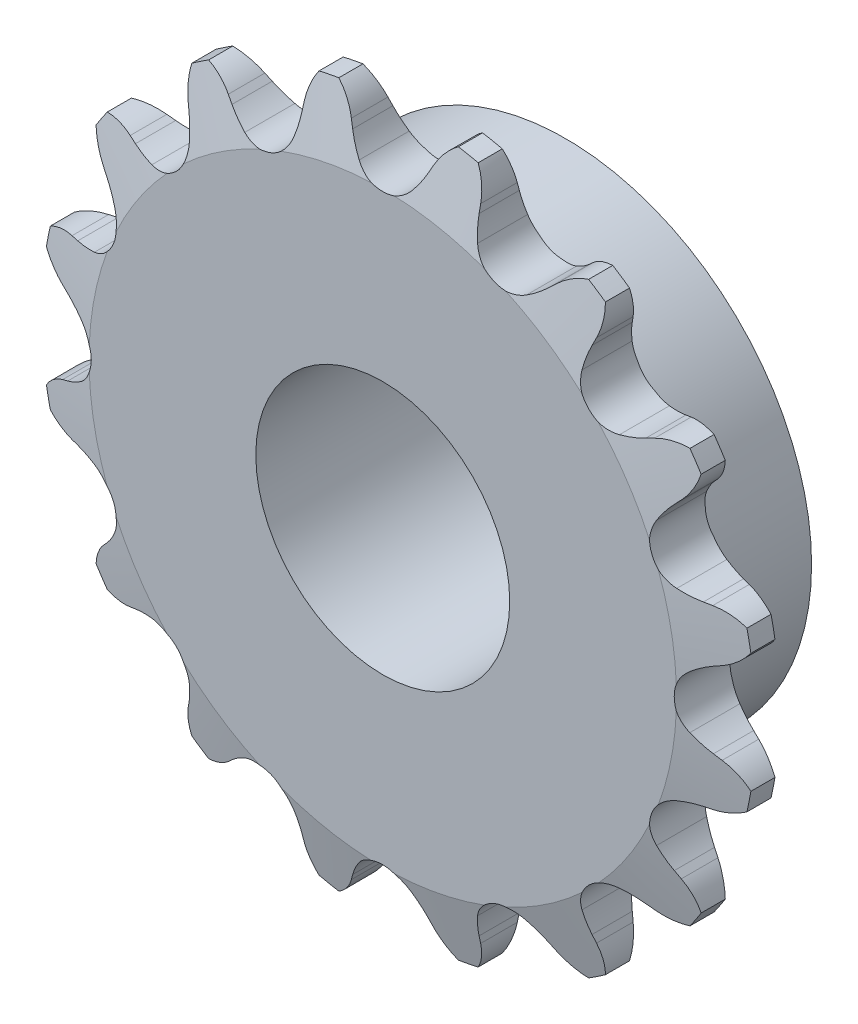
SolidWorks part; units mm, degrees
ref_plane "Front Plane" through (0, 0, 0) normal (0, 0, 1) x (1, 0, 0)
ref_plane "Top Plane" through (0, 0, 0) normal (0, 1, 0) x (1, 0, 0)
ref_plane "Right Plane" through (0, 0, 0) normal (1, 0, 0) x (0, 0, -1)
ref_axis "Axis1" through (0, 0, -88.99) along (0, 0, 1)
sketch "Sprocket-BaseSketch" plane through (0, 0, 0) normal (1, 0, 0) x (0, 0, -1)
  line L0 (1.397, 0) -> (1.397, 14.6918)
  line L1 (1.397, 14.6918) -> (0.6032, 17.8668)
  line L2 (0.6032, 17.8668) -> (-0.6032, 17.8668)
  line L3 (-0.6032, 17.8668) -> (-1.397, 14.6918)
  line L4 (-1.397, 14.6918) -> (-1.397, 0)
  line L5 (-1.397, 0) -> (1.397, 0)
  line L6 (5.588, 0) -> (-1.7463, 0) construction
  dimension "Hub Surface" = 1.397
  dimension "RightSide (1)" = 0.7938
  dimension "RightSide (2)" = 3.175
  dimension "OD" = 17.8668
  dimension "LeftSide (1)" = 0.7938
  dimension "LeftSide (2)" = 3.175
  dimension "Tooth Width" = 2.794
revolve "25 (04C) ANSI (ISO) Chain Number, 1.281in P.D." add sketch "Sprocket-BaseSketch" angle 360 about L6
sketch "Tooth-Sketch" plane through (0, 0, 0) normal (0, 0, 1) x (1, 0, 0)
  line L0 (0, 0) -> (0, 21.6994) construction
  line L1 (1.896, 16.1459) -> (2.0514, 16.491)
  line L2 (-1.896, 16.1459) -> (-2.0514, 16.491)
  line L3 (0, 16.2745) -> (6.228, 15.0357) construction
  line L4 (0, 16.2745) -> (-6.228, 15.0357) construction
  arc A0 (-1.3237, 15.2121) -> (1.3237, 15.2121) centre (0, 16.2745) ccw
  arc A1 (1.3237, 15.2121) -> (1.896, 16.1459) centre (-2.0601, 17.928) ccw
  arc A2 (-1.3237, 15.2121) -> (-1.896, 16.1459) centre (2.0601, 17.928) cw
  arc A3 (2.0514, 16.491) -> (4.534, 18.0955) centre (4.534, 15.3726) cw
  arc A4 (-2.0514, 16.491) -> (-4.534, 18.0955) centre (-4.534, 15.3726) ccw
  arc A5 (4.534, 18.0955) -> (-4.534, 18.0955) centre (0, 0) ccw
extrude "Tooth-Cut, Number of teeth: 16" cut sketch "Tooth-Sketch" against normal through all and the other way through all
pattern_circular "Tooth Pattern, 16 / 16" count 16 every 22.5 about axis through (0, 0, -88.99) along (0, 0, 1) of "Tooth-Cut, Number of teeth: 16"
sketch "Sketch3" plane through (0, 0, 0) normal (1, 0, 0) x (0, 0, -1)
  line L0 (-9.906, 0) -> (9.906, 0) construction
  line L1 (1.397, 0) -> (1.397, 12.3031)
  line L2 (1.397, 12.3031) -> (11.303, 12.3031)
  line L3 (11.303, 12.3031) -> (11.303, 0)
  line L4 (11.303, 0) -> (1.397, 0)
  dimension "Hub Mounting" = 1.397
  dimension "Hub OD" = 12.3031
  dimension "Hub Width" = 9.906
revolve "Hub-Revolve1" add sketch "Sketch3" angle 360 about L0
sketch "Sketch4" plane through (0, 0, -11.303) normal (0, 0, -1) x (-1, 0, 0)
  circle A0 centre (0, 0) radius 6.35
  dimension "Bore Diameter " = 12.7
extrude "Cut-Extrude1" cut sketch "Sketch4" against normal through all
sketch "Sketch5" [suppressed] plane through (0, 0, 0) normal (1, 0, 0) x (0, 0, -1)
  line L0 (11.303, 0) -> (-1.397, 0) construction
  line L1 (11.303, -12.3031) -> (11.303, 12.3031) construction
  line L2 (-1.397, 0.5825) -> (-1.397, -0.5825) construction
ref_plane "Plane1" [suppressed] through (0, 0, 0) normal (-0.1951, 0.9808, 0) x (-0.9808, -0.1951, 0)
sketch "Sketch7" [suppressed] plane through (0, 0, 0) normal (1, 0, 0) x (0, 0, -1)
  line L0 (11.303, 0) -> (11.303, 6.35) construction
ref_plane "Plane2" [suppressed] through (-1.215, 6.1083, 0) normal (-0.1951, 0.9808, 0) x (-0.9808, -0.1951, 0)
sketch "Sketch8" [suppressed] plane through (-1.215, 6.1083, 0) normal (-0.1951, 0.9808, 0) x (-0.9808, -0.1951, 0)
  line L0 (-12.3031, -6.35) -> (12.3031, -6.35) construction
  line L1 (-12.3031, -1.397) -> (-12.3031, -11.303) construction
  line L2 (12.3031, -11.303) -> (12.3031, -1.397) construction
  line L3 (0, -6.35) -> (0, -1.397) construction
  line L4 (-12.3031, -1.397) -> (12.3031, -1.397) construction
  line L5 (0, -3.8735) -> (0, -6.35) construction
  circle A0 centre (0, -6.35) radius 2.4765
extrude "Cut-Extrude2" [suppressed] cut sketch "Sketch8" along normal through all draft 1 and the other way blind 2.54 draft 1 draft outward yes
sketch "Sketch9" [suppressed] plane through (-1.215, 6.1083, 0) normal (-0.1951, 0.9808, 0) x (-0.9808, -0.1951, 0)
  line L0 (0, -6.35) -> (2.4699, -6.35) construction
  line L1 (2.4699, -6.35) -> (2.5775, -6.35) construction
  line L2 (2.5237, -6.35) -> (2.5237, -11.303) construction
  line L3 (-12.3031, -11.303) -> (12.3031, -11.303) construction
  circle A0 centre (0, -6.35) radius 2.5237
  circle A1 centre (0, -6.35) radius 2.4765 construction
  spline S0 degree 3 poles (2.1142, -7.6418) (2.2645, -7.3531) (2.3246, -7.2033) (2.4154, -6.8925) (2.4462, -6.7295) (2.4747, -6.4042) (2.4729, -6.2415) (2.4372, -5.9161) (2.403, -5.7545) (2.3055, -5.446) (2.2414, -5.2961) (2.0857, -5.0123) (1.9953, -4.8802) (1.79, -4.6344) (1.6738, -4.5202) (1.425, -4.319) (1.2915, -4.2309) (1.0052, -4.0801) (0.8533, -4.0183) (0.5434, -3.9267) (0.3835, -3.8958) (0.0549, -3.8665) (-0.1081, -3.8684) (-0.4316, -3.904) (-0.5939, -3.9386) (-0.9034, -4.0373) (-1.0516, -4.1013) (-1.335, -4.2582) (-1.4684, -4.3505) (-1.7127, -4.5568) (-1.8255, -4.6725) (-2.0267, -4.9241) (-2.114, -5.0581) (-2.2626, -5.3429) (-2.3242, -5.4956) (-2.4153, -5.807) (-2.4455, -5.9661) (-2.4746, -6.2915) (-2.4729, -6.4579) (-2.4376, -6.7814) (-2.4042, -6.9412) (-2.3058, -7.2535) (-2.2423, -7.4019) (-2.0879, -7.6841) (-1.9959, -7.819) (-1.7906, -8.0649) (-1.6769, -8.177) (-1.4268, -8.3797) (-1.291, -8.4693) (-0.865, -8.6939) (-0.5448, -8.7895) (-0.0591, -8.8333) (0.1071, -8.8317) (0.4324, -8.7959) (0.5913, -8.7621) (0.9016, -8.6634) (1.0524, -8.5982) (1.3339, -8.4424) (1.467, -8.3507) (1.7137, -8.1423) (1.8251, -8.0278) (2.0252, -7.7781) (2.1142, -7.6418) (2.2645, -7.3531) (2.3246, -7.2033) knots -0.03125 -0.03125 0 0 0.03125 0.03125 0.0625 0.0625 0.09375 0.09375 0.125 0.125 0.15625 0.15625 0.1875 0.1875 0.21875 0.21875 0.25 0.25 0.28125 0.28125 0.3125 0.3125 0.34375 0.34375 0.375 0.375 0.40625 0.40625 0.4375 0.4375 0.46875 0.46875 0.5 0.5 0.53125 0.53125 0.5625 0.5625 0.59375 0.59375 0.625 0.625 0.65625 0.65625 0.6875 0.6875 0.71875 0.71875 0.75 0.75 0.8125 0.8125 0.84375 0.84375 0.875 0.875 0.90625 0.90625 0.9375 0.9375 0.96875 0.96875 1 1 1.03125 1.03125 1.0625 only from (2.1894, -7.4975) to (2.1894, -7.4975) construction
  spline S1 degree 3 poles (2.1222, -7.8259) (2.2972, -7.534) (2.3695, -7.3811) (2.4837, -7.0617) (2.5252, -6.8956) (2.5992, -6.3956) (2.5821, -6.0484) (2.4595, -5.5586) (2.4018, -5.3971) (2.2574, -5.0917) (2.1712, -4.9478) (1.9711, -4.6772) (1.8563, -4.5502) (1.6078, -4.3244) (1.4733, -4.224) (1.1827, -4.049) (1.0293, -3.9763) (0.7127, -3.8624) (0.5468, -3.8205) (0.211, -3.7705) (0.0426, -3.7623) (-0.2948, -3.7788) (-0.4653, -3.8043) (-0.7923, -3.8867) (-0.9505, -3.9435) (-1.2564, -4.0886) (-1.4024, -4.1766) (-1.806, -4.4769) (-2.0375, -4.7327) (-2.2966, -5.1651) (-2.3699, -5.3201) (-2.4837, -5.6382) (-2.5246, -5.8014) (-2.5745, -6.1366) (-2.5829, -6.3082) (-2.5664, -6.6449) (-2.5419, -6.8119) (-2.4592, -7.1429) (-2.4022, -7.3018) (-2.2589, -7.6055) (-2.1714, -7.752) (-1.9705, -8.0235) (-1.8581, -8.1479) (-1.6095, -8.3743) (-1.4721, -8.4767) (-1.184, -8.6502) (-1.0322, -8.7226) (-0.7127, -8.8377) (-0.5474, -8.8793) (-0.2143, -8.9291) (-0.0435, -8.9378) (0.2961, -8.9211) (0.4627, -8.8962) (0.7897, -8.8142) (0.9516, -8.7561) (1.2559, -8.6116) (1.3997, -8.5253) (1.6706, -8.324) (1.7969, -8.2093) (2.0219, -7.9607) (2.1222, -7.8259) (2.2972, -7.534) (2.3695, -7.3811) knots -0.03125 -0.03125 0 0 0.03125 0.03125 0.0625 0.0625 0.125 0.125 0.15625 0.15625 0.1875 0.1875 0.21875 0.21875 0.25 0.25 0.28125 0.28125 0.3125 0.3125 0.34375 0.34375 0.375 0.375 0.40625 0.40625 0.4375 0.4375 0.5 0.5 0.53125 0.53125 0.5625 0.5625 0.59375 0.59375 0.625 0.625 0.65625 0.65625 0.6875 0.6875 0.71875 0.71875 0.75 0.75 0.78125 0.78125 0.8125 0.8125 0.84375 0.84375 0.875 0.875 0.90625 0.90625 0.9375 0.9375 0.96875 0.96875 1 1 1.03125 1.03125 1.0625 only from (2.2097, -7.68) to (2.2097, -7.68) construction
extrude "Extrude1" [suppressed] add sketch "Sketch9" along normal up to surface and the other way blind 2.54
sketch "Sketch10" [suppressed] plane through (-1.215, 6.1083, 0) normal (-0.1951, 0.9808, 0) x (-0.9808, -0.1951, 0)
  line L0 (0, -6.35) -> (2.5237, -6.35) construction
  line L1 (1.2618, -6.35) -> (1.2618, -4.1644) construction
  line L3 (0, -4.8929) -> (-1.2618, -5.6215)
  line L4 (-1.2618, -5.6215) -> (-1.2618, -7.0785)
  line L5 (-1.2618, -7.0785) -> (0, -7.8071)
  line L6 (0, -7.8071) -> (1.2618, -7.0785)
  line L7 (1.2618, -7.0785) -> (1.2618, -5.6215)
  line L8 (1.2618, -5.6215) -> (0, -4.8929)
  circle A0 centre (0, -6.35) radius 2.5237 construction
  circle A1 centre (0, -6.35) radius 1.2618 construction
extrude "Cut-Extrude3" [suppressed] cut sketch "Sketch10" along normal through all from offset 2.54
pattern_circular "CirPattern1" [suppressed] count 2 over 90 about axis through (0, 0, 9.906) along (0, 0, -1) of bodies 108
sketch "Sketch11" plane through (0, 0, -11.303) normal (0, 0, -1) x (-1, 0, 0)
  circle A0 centre (0, 0) radius 6.35
  circle A1 centre (0, 0) radius 6.35 construction
extrude "Cut-Extrude4" cut sketch "Sketch11" against normal through all rebuild error yes
sketch "Sketch12" [suppressed] plane through (0, 0, -11.303) normal (0, 0, -1) x (-1, 0, 0)
  line L0 (-17.5235, 3.4856) -> (17.5235, -3.4856)
  line L1 (-6.228, -15.0357) -> (0, -16.2745)
  line L2 (6.8508, -1.3627) -> (-6.8508, 1.3627) construction
  line L3 (-17.7837, 2.1778) -> (17.2633, -4.7935)
  line L4 (-5.9678, -13.7278) -> (0.2602, -14.9666)
  circle A0 centre (0, 0) radius 17.8668
  arc A1 (15.1301, 9.5028) -> (14.5694, 10.3419) centre (0, 0) ccw construction
  dimension "D1" = 1.3335
  dimension "D2" = 1.3335
sketch "Sketch13" plane through (0, 0, -11.303) normal (0, 0, -1) x (-1, 0, 0)
  circle A0 centre (0, 0) radius 6.35
  circle A1 centre (0, 0) radius 12.3031
extrude "Cut-Extrude5" cut sketch "Sketch13" against normal blind 3.556
equation "\"D1@Sketch12\" = \"D2@Sketch12\""
